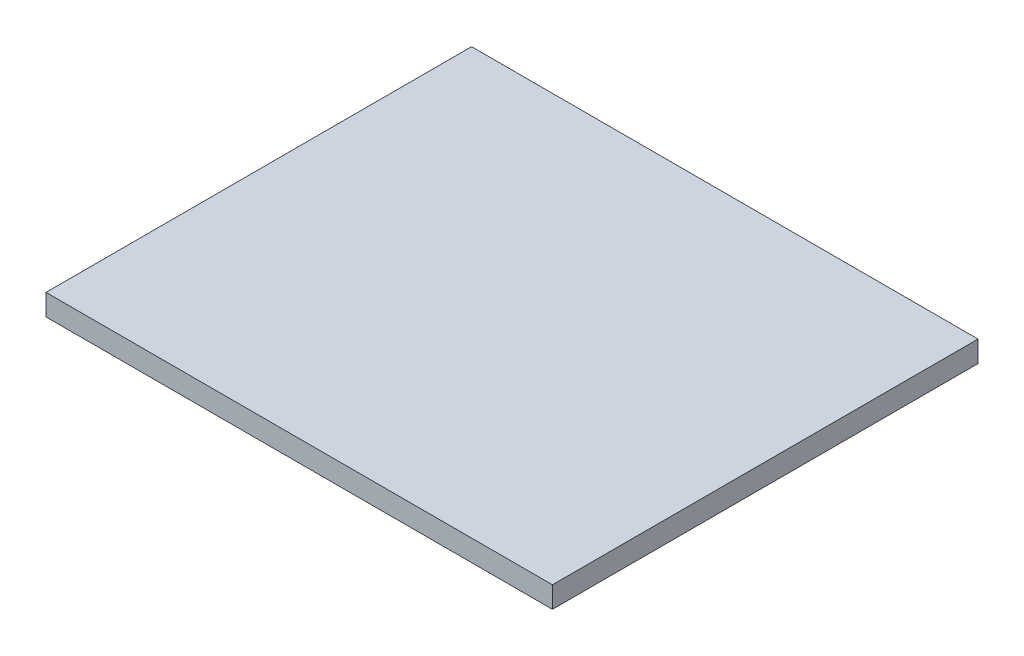
SolidWorks part; units mm, degrees
ref_plane "Front Plane" through (0, 0, 0) normal (0, 0, 1) x (1, 0, 0)
ref_plane "Top Plane" through (0, 0, 0) normal (0, 1, 0) x (1, 0, 0)
ref_plane "Right Plane" through (0, 0, 0) normal (1, 0, 0) x (0, 0, -1)
sketch "Sketch1" plane through (0, 0, 0) normal (0, 1, 0) x (1, 0, 0)
  line L6 (-29.75, 25) -> (29.75, 25)
  line L28 (-29.75, 25) -> (-29.75, -25)
  line L29 (-29.75, -25) -> (29.75, -25)
  line L30 (29.75, 25) -> (29.75, -25)
  line L31 (-29.75, 25) -> (29.75, -25) construction
  line L32 (-29.75, -25) -> (29.75, 25) construction
  circle A1 centre (0, 0) radius 3
  point P0 (0, 0)
  dimension "D3" = 6
  dimension "D1" = 59.5
  dimension "D2" = 50
extrude "Boss-Extrude1" add sketch "Sketch1" along normal blind 1.5
sketch "Sketch2" plane through (0, 0, -25) normal (0, 0, -1) x (-1, 0, 0)
  line L0 (-29.75, 1.5) -> (-29.75, 0) construction
  line L1 (-29.75, 1.5) -> (29.75, 1.5)
  line L2 (-29.75, 1.5) -> (-29.75, 2.5)
  line L4 (29.75, 1.5) -> (29.75, 2.5)
  line L5 (-1.19, 2.5) -> (0, 4)
  line L6 (0, 0.825) -> (0, -0.825) construction
  line L7 (1.19, 2.5) -> (0, 4)
  line L8 (1.19, 2.5) -> (2.38, 4)
  line L9 (3.57, 2.5) -> (2.38, 4)
  line L10 (3.57, 2.5) -> (4.76, 4)
  line L11 (5.95, 2.5) -> (4.76, 4)
  line L12 (5.95, 2.5) -> (7.14, 4)
  line L13 (8.33, 2.5) -> (7.14, 4)
  line L14 (8.33, 2.5) -> (9.52, 4)
  line L15 (10.71, 2.5) -> (9.52, 4)
  line L16 (10.71, 2.5) -> (11.9, 4)
  line L17 (13.09, 2.5) -> (11.9, 4)
  line L18 (13.09, 2.5) -> (14.28, 4)
  line L19 (15.47, 2.5) -> (14.28, 4)
  line L20 (15.47, 2.5) -> (16.66, 4)
  line L21 (17.85, 2.5) -> (16.66, 4)
  line L22 (17.85, 2.5) -> (19.04, 4)
  line L23 (20.23, 2.5) -> (19.04, 4)
  line L24 (20.23, 2.5) -> (21.42, 4)
  line L25 (22.61, 2.5) -> (21.42, 4)
  line L26 (22.61, 2.5) -> (23.8, 4)
  line L27 (24.99, 2.5) -> (23.8, 4)
  line L28 (24.99, 2.5) -> (26.18, 4)
  line L29 (27.37, 2.5) -> (26.18, 4)
  line L30 (27.37, 2.5) -> (28.56, 4)
  line L31 (29.75, 2.5) -> (28.56, 4)
  line L32 (-29.75, 2.5) -> (-28.56, 4)
  line L33 (-27.37, 2.5) -> (-28.56, 4)
  line L34 (-27.37, 2.5) -> (-26.18, 4)
  line L35 (-24.99, 2.5) -> (-26.18, 4)
  line L36 (-24.99, 2.5) -> (-23.8, 4)
  line L37 (-22.61, 2.5) -> (-23.8, 4)
  line L38 (-22.61, 2.5) -> (-21.42, 4)
  line L39 (-20.23, 2.5) -> (-21.42, 4)
  line L40 (-20.23, 2.5) -> (-19.04, 4)
  line L41 (-17.85, 2.5) -> (-19.04, 4)
  line L42 (-17.85, 2.5) -> (-16.66, 4)
  line L43 (-15.47, 2.5) -> (-16.66, 4)
  line L44 (-15.47, 2.5) -> (-14.28, 4)
  line L45 (-13.09, 2.5) -> (-14.28, 4)
  line L46 (-13.09, 2.5) -> (-11.9, 4)
  line L47 (-10.71, 2.5) -> (-11.9, 4)
  line L48 (-10.71, 2.5) -> (-9.52, 4)
  line L49 (-8.33, 2.5) -> (-9.52, 4)
  line L50 (-8.33, 2.5) -> (-7.14, 4)
  line L51 (-5.95, 2.5) -> (-7.14, 4)
  line L52 (-5.95, 2.5) -> (-4.76, 4)
  line L53 (-3.57, 2.5) -> (-4.76, 4)
  line L54 (-3.57, 2.5) -> (-2.38, 4)
  line L55 (-1.19, 2.5) -> (-2.38, 4)
  dimension "D1" = 1
  dimension "D2" = 1.5
  dimension "D3" = 13
extrude "Boss-Extrude2" add sketch "Sketch2" against normal blind 50
sketch "Sketch3" plane through (0, 0, 0) normal (0, -1, 0) x (-1, 0, 0)
  line L0 (0, 2.2) -> (0, -2.2) construction
  line L2 (-1.75, -2.4367) -> (-1.75, -5)
  line L3 (-1.75, -5) -> (1.75, -5)
  line L4 (1.75, -2.4367) -> (1.75, -5)
  arc A0 (1.75, -2.4367) -> (-1.75, -2.4367) centre (0, 0) ccw
  dimension "D2" = 6
  dimension "D1" = 3.5
  dimension "D3" = 5
  dimension "D4" = 1.75
extrude "Cut-Extrude1" cut sketch "Sketch3" against normal blind 2
chamfer "Chamfer1" distance 2 angle 45 1 edges at (0, 0, 5)
sketch "Sketch4" plane through (0, 0, 25) normal (0, 0, 1) x (1, 0, 0)
  line L1 (-29.75, 2.5) -> (29.75, 2.5)
  line L2 (-29.75, 2.5) -> (-29.75, 4.3927)
  line L3 (-29.75, 4.3927) -> (29.75, 4.3927)
  line L4 (29.75, 2.5) -> (29.75, 4.3927)
extrude "Cut-Extrude2" cut sketch "Sketch4" against normal through all
